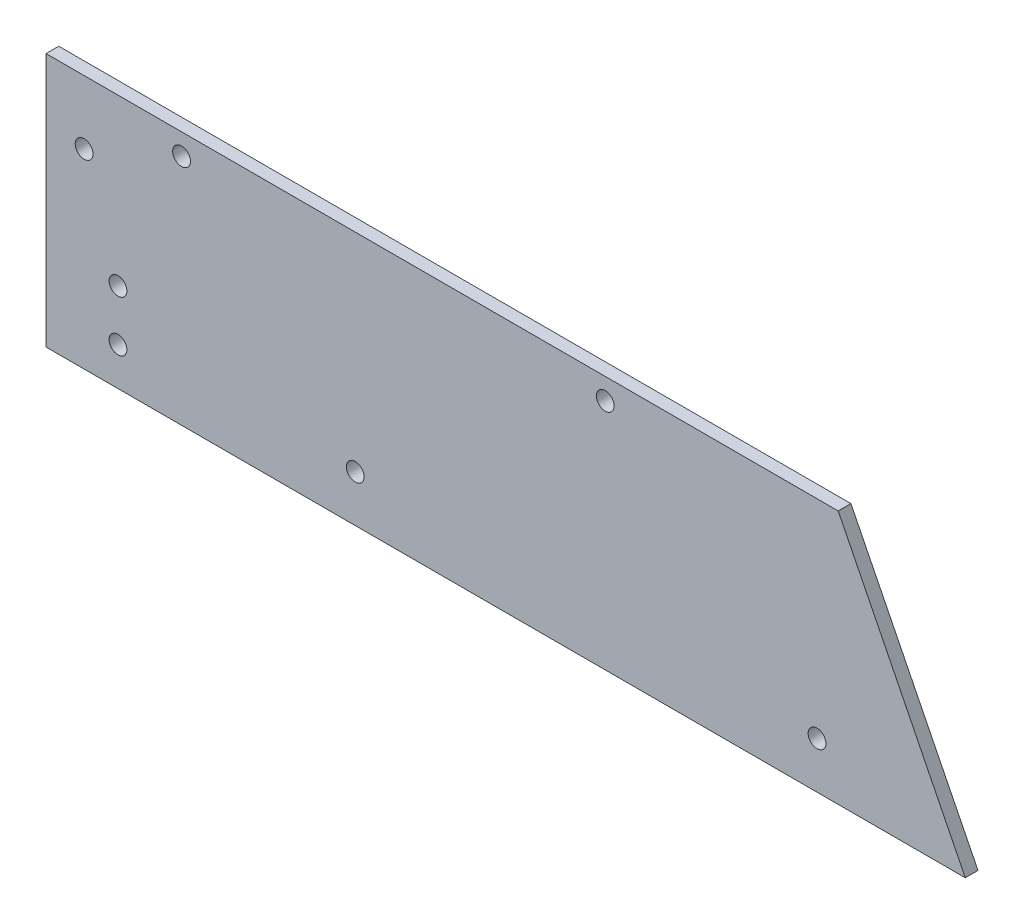
SolidWorks part; units mm, degrees
ref_plane "Płaszczyzna przednia" through (0, 0, 0) normal (0, 0, 1) x (1, 0, 0)
ref_plane "Płaszczyzna górna" through (0, 0, 0) normal (0, 1, 0) x (1, 0, 0)
ref_plane "Płaszczyzna prawa" through (0, 0, 0) normal (1, 0, 0) x (0, 0, -1)
sketch "Szkic1" plane through (0, 0, 0) normal (0, 0, 1) x (1, 0, 0)
  line L1 (0, 0) -> (217, 0)
  line L2 (0, 0) -> (0, 60)
  line L3 (0, 60) -> (217, 60)
  line L4 (217, 0) -> (217, 60)
  dimension "D1" = 217
  dimension "D2" = 60
extrude "Dodanie-wyciągnięcie1" add sketch "Szkic1" along normal blind 3
sketch "Szkic2" plane through (0, 0, 3) normal (0, 0, 1) x (1, 0, 0)
  line L0 (217, 0) -> (187, 60)
  line L1 (217, 60) -> (0, 60) construction
  line L2 (217, 0) -> (217, 60) construction
  line L3 (217, 0) -> (217, 60)
  line L4 (217, 60) -> (0, 60)
  line M3 (217, 0) -> (217, 60)
  line M4 (217, 60) -> (0, 60)
  dimension "D1" = 30
extrude "Wytnij-wyciągnięcie1" cut sketch "Szkic2" against normal blind 3 contours L0 M3 M4 region at (207, 40, 3)
sketch "Szkic3" plane through (0, 0, 3) normal (0, 0, 1) x (1, 0, 0)
  line L0 (17, 67.4213) -> (17, -16.319) construction
  line L1 (0, 60) -> (0, 0) construction
  line L2 (0, 0) -> (217, 0) construction
  circle A0 centre (17, 9) radius 2.1
  circle A1 centre (17, 21) radius 2.1
  dimension "D2" = 4.2
  dimension "D3" = 9
  dimension "D4" = 12
  dimension "D1" = 17
extrude "Wytnij-wyciągnięcie2" cut sketch "Szkic3" against normal blind 3
sketch "Szkic4" plane through (0, 0, 3) normal (0, 0, 1) x (1, 0, 0)
  line L0 (0, 60) -> (0, 0) construction
  line L1 (0, 0) -> (217, 0) construction
  circle A0 centre (73, 11) radius 2.1
  circle A1 centre (182, 11) radius 2.1
  dimension "D2" = 109
  dimension "D3" = 4.2
  dimension "D4" = 11
  dimension "D1" = 73
extrude "Wytnij-wyciągnięcie3" cut sketch "Szkic4" against normal blind 10
sketch "Szkic5" plane through (0, 0, 3) normal (0, 0, 1) x (1, 0, 0)
  line L0 (0, 60) -> (0, 0) construction
  line L1 (187, 60) -> (0, 60) construction
  circle A0 centre (32, 55) radius 2.1
  circle A1 centre (132, 55) radius 2.1
  dimension "D2" = 100
  dimension "D3" = 4.2
  dimension "D4" = 5
  dimension "D1" = 32
extrude "Wytnij-wyciągnięcie4" cut sketch "Szkic5" against normal blind 10
sketch "Szkic6" plane through (0, 0, 3) normal (0, 0, 1) x (1, 0, 0)
  line L0 (0, 60) -> (0, 0) construction
  line L1 (187, 60) -> (0, 60) construction
  circle A0 centre (9, 45) radius 2.1
  dimension "D1" = 4.2
  dimension "D2" = 9
  dimension "D3" = 15
extrude "Wytnij-wyciągnięcie5" cut sketch "Szkic6" against normal blind 10
